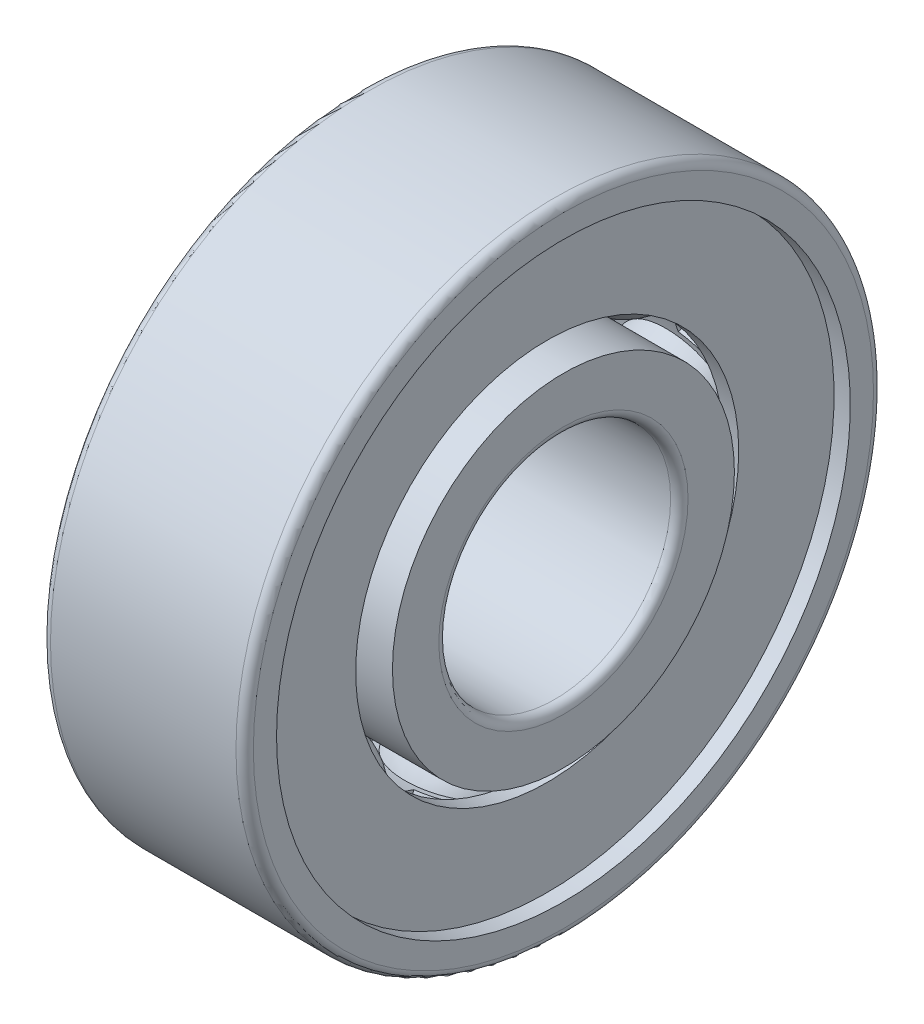
SolidWorks part; units mm, degrees
revolve "凸台-旋转2" add sketch "草图6" angle 360 about L4
sketch "草图6" plane through (0, 0, 0) normal (0, 0, 1) x (1, 0, 0)
  line L0 (0, 0) -> (5.5439, 0) construction
  line L1 (-12.4206, 0) -> (9.8128, 0) construction
  line L2 (0, 0) -> (0, 11.4011) construction
  line L3 (-5.5681, 7.9) -> (6.1049, 7.9) construction
  line L4 (-5.5681, 7.9) -> (6.1049, 7.9) construction
  line L5 (-2.15, 7.9) -> (2.15, 7.9)
  arc A0 (-2.15, 7.9) -> (2.15, 7.9) centre (0, 7.9) ccw
  dimension "Dw" = 4.3
revolve "基体-旋转" add sketch "草图2" angle 360 about L0
sketch "草图2" plane through (0, 0, 0) normal (0, 0, 1) x (1, 0, 0)
  line L0 (-12.4206, 0) -> (9.8128, 0) construction
  line L1 (0, 0) -> (0, 37.3563) construction
  line L2 (-5.5681, 7.9) -> (6.1049, 7.9) construction
  line L3 (-0.473, 8.4913) -> (0.473, 8.4913)
  line L4 (-0.473, 8.4913) -> (-0.473, 7.3088)
  line L5 (-0.473, 7.3088) -> (0.473, 7.3088)
  line L6 (0.473, 8.4913) -> (0.473, 7.3088)
  dimension "D1" = 0.946
  dimension "D2" = 0.473
  dimension "D3" = 1.1825
  dimension "D4" = 0.5913
  dimension "D5" = 7.9
revolve "凸台-旋转1" add sketch "草图3" angle 360 about L1
sketch "草图3" plane through (0, 0, 0) normal (0, 0, 1) x (1, 0, 0)
  line L0 (-5.5681, 7.9) -> (6.1049, 7.9) construction
  line L1 (-5.5681, 7.9) -> (6.1049, 7.9) construction
  line L2 (-12.4206, 0) -> (9.8128, 0) construction
  line L3 (-12.4206, 0) -> (9.8128, 0) construction
  line L4 (0, 0) -> (0, 37.3563) construction
  line L5 (0, 0) -> (0, 37.3563) construction
  line L6 (-2.365, 7.9) -> (2.365, 7.9)
  arc A0 (-2.365, 7.9) -> (2.365, 7.9) centre (0, 7.9) ccw
  dimension "Dwww" = 4.73
  dimension "D2" = 2.365
pattern_circular "阵列(圆周)1" count 8 over 360 about axis through (-12.4206, 0, 0) along (1, 0, 0) of "凸台-旋转1"
revolve "凸台-旋转3" add sketch "草图7" angle 360 about L0
sketch "草图7" plane through (0, 0, 0) normal (0, 0, 1) x (1, 0, 0)
  line L0 (0, 0) -> (6.6488, 0) construction
  line L1 (0, 0) -> (0, 16.8954) construction
  line L2 (-3.2, 11) -> (3.2, 11)
  line L3 (-3.5, 10.7) -> (-3.5, 9.9)
  line L4 (-3.5, 9.9) -> (-0.7613, 9.9)
  line L5 (3.5, 10.7) -> (3.5, 9.9)
  line L6 (0.7613, 9.9) -> (2.4048, 9.9)
  line L7 (2.94, 9.9) -> (3.5, 9.9)
  line L8 (2.4048, 9.65) -> (2.94, 9.65)
  line L9 (2.4048, 9.65) -> (2.4048, 9.9)
  line L11 (2.94, 9.65) -> (2.94, 9.9)
  arc A0 (-3.2, 11) -> (-3.5, 10.7) centre (-3.2, 10.7) ccw
  arc A1 (3.2, 11) -> (3.5, 10.7) centre (3.2, 10.7) cw
  arc A2 (2.0671, 8.4912) -> (-2.0671, 8.4913) centre (0, 7.9) ccw construction
  arc A3 (0.789, 9.9) -> (-0.0001, 10.05) centre (0, 7.9) ccw construction
  arc A4 (0.7613, 9.9) -> (-0.7613, 9.9) centre (0, 7.9) ccw
  point P10 (-3.5, 11)
  point P13 (3.5, 11)
  dimension "D3" = 3.5
  dimension "D4" = 0.5352
  dimension "D5" = 19.3
  dimension "D6" = 0.56
  dimension "B" = 7
ref_plane "基准面1" through (0, 0, 0) normal (0, 0, 1) x (1, 0, 0)
ref_plane "基准面2" through (0, 0, 0) normal (0, 1, 0) x (1, 0, 0)
ref_plane "基准面3" through (0, 0, 0) normal (1, 0, 0) x (0, 0, -1)
sketch "尺寸草图" plane through (0, 0, 0) normal (0, 0, 1) x (1, 0, 0)
  point P0 (0, -75.4307)
  point P1 (4.3, -75.4307)
  point P2 (0, 50.7088)
  point P3 (8, 50.7088)
  point P4 (22, 50.7088)
  point P5 (7, 50.7088)
  point P6 (0, -10.9899)
  point P7 (11.8, -10.9899)
  point P8 (19.3, -10.9899)
  point P9 (0.3, -10.9899)
  point P10 (8, -75.4307)
  dimension "B" = 7
sketch "草图4" plane through (0, 0, 0) normal (0, 0, 1) x (1, 0, 0)
  line L0 (0, 0) -> (8.1272, 0) construction
  line L1 (-12.4206, 0) -> (9.8128, 0) construction
  line L3 (-0.473, 8.4913) -> (0.473, 8.4913) construction
  line L4 (-2.365, 10.8563) -> (2.365, 10.8563)
  line L5 (-2.365, 10.8563) -> (-2.365, 8.4913)
  line L6 (-2.365, 8.4913) -> (2.365, 8.4913)
  line L7 (2.365, 10.8563) -> (2.365, 8.4913)
revolve "切除-旋转1" cut sketch "草图4" angle 360 about L0
sketch "草图5" plane through (0, 0, 0) normal (0, 0, 1) x (1, 0, 0)
  line L0 (0, 0) -> (8.2665, 0) construction
  line L1 (-12.4206, 0) -> (9.8128, 0) construction
  line L2 (-0.473, 7.3088) -> (0.473, 7.3088) construction
  line L3 (-2.365, 7.3088) -> (2.365, 7.3088)
  line L4 (-2.365, 7.3088) -> (-2.365, 4.9438)
  line L5 (-2.365, 4.9438) -> (2.365, 4.9438)
  line L6 (2.365, 7.3088) -> (2.365, 4.9438)
revolve "切除-旋转2" cut sketch "草图5" angle 360 about L0
pattern_circular "阵列(圆周)2" count 8 over 360 about axis through (-12.4206, 0, 0) along (1, 0, 0) of "凸台-旋转2"
sketch "草图8" plane through (0, 0, 0) normal (0, 0, 1) x (1, 0, 0)
  line L0 (-12.4206, 0) -> (9.8128, 0) construction
  line L1 (-12.4206, 0) -> (9.8128, 0) construction
  line L2 (3.5, 10.7) -> (3.5, 9.9) construction
  line L3 (-3.5, 5.9) -> (-0.7613, 5.9)
  line L4 (-3.5, 5.9) -> (-3.5, 4.3)
  line L5 (-3.2, 4) -> (3.2, 4)
  line L6 (3.5, 5.9) -> (3.5, 4.3)
  line L7 (-3.5, 10.7) -> (-3.5, 9.9) construction
  line L8 (0.7613, 5.9) -> (3.5, 5.9)
  arc A0 (-3.5, 4.3) -> (-3.2, 4) centre (-3.2, 4.3) ccw
  arc A1 (3.2, 4) -> (3.5, 4.3) centre (3.2, 4.3) ccw
  arc A2 (-2.0671, 7.3087) -> (2.0671, 7.3087) centre (0, 7.9) ccw construction
  arc A3 (-2.0671, 7.3087) -> (2.0671, 7.3087) centre (0, 7.9) ccw construction
  arc A4 (-0.7613, 5.9) -> (0.7613, 5.9) centre (0, 7.9) ccw
  dimension "D1" = 0.3
  dimension "DD" = 8
  dimension "D2" = 0.01
revolve "凸台-旋转4" add sketch "草图8" angle 360 about L1
sketch "草图10" plane through (0, 0, 0) normal (0, 0, 1) x (1, 0, 0)
  line L0 (2.4048, 9.9) -> (2.4048, -9.9) construction
  line L1 (2.94, 9.65) -> (2.4048, 9.65)
  line L2 (2.94, 9.65) -> (2.94, 6.6095)
  line L3 (2.94, 6.6095) -> (2.4048, 6.6095)
  line L4 (2.4048, 9.65) -> (2.4048, 6.6095)
  line L5 (0.7613, 5.9) -> (3.5, 5.9) construction
  line L6 (0, 0) -> (-5.3515, 0) construction
  line L7 (-12.4206, 0) -> (9.8128, 0) construction
  dimension "D1" = 0.7095
revolve "凸台-旋转5" add sketch "草图10" angle 360 about L6
sketch "草图11" plane through (0, 0, 0) normal (1, 0, 0) x (0, 0, -1)
  circle A0 centre (0, 0) radius 11
  circle A1 centre (0, 0) radius 11 construction
extrude "切除-拉伸1" cut sketch "草图11" against normal blind 10
mirror "镜向所有1" about plane through (0, 0, 0) normal (1, 0, 0) of bodies 109
equation "\"D5@草图7\" = \"防尘圈径D3@尺寸草图\""
equation "\"Z@阵列(圆周)1\"=\"球数Z@尺寸草图\" "
equation "\"Dw@草图6\"=\"球径DW@尺寸草图\""
equation "\"DD@草图8\"=\"d@尺寸草图\""
equation "\"D@草图7\"=\"DD@尺寸草图\""
equation "\"B@草图7\"=\"B@尺寸草图\" "
equation "\"DD2@草图8\"=\"内圈外径DD2@尺寸草图\""
equation "\"R@草图7\"=\"r@尺寸草图\""
equation "\"D3@草图2\" = 0.25*\"Dwww@草图3\""
equation "\"D4@草图2\" = \"D3@草图2\"/2"
equation "\"Dwww@草图3\" = 1.1*\"Dw@草图6\""
equation "\"D2@草图3\" = 0.5*\"Dwww@草图3\""
equation "\"D1@草图2\" = 0.2*\"Dwww@草图3\""
equation "\"D2@草图2\" = 0.5*\"D1@草图2\""
equation "\"切除位置@草图4\" = \"Dwww@草图3\"/2"
equation "\"D1@阵列(圆周)2\" = \"Z@阵列(圆周)1\""
equation "\"D3@草图7\" = \"B@草图7\" / 2"
equation "\"D1@草图8\" = \"R@草图7\""
equation "\"D2@草图7\" = 0.9*\"D@草图7\""
equation "\"D5@草图2\" = 0.25* ( \"D2@草图7\" + \"DD2@草图8\" )  "
equation "\"D6@草图7\" = 0.08 * \"B@草图7\""
equation "\"D1@草图10\" = 0.15*\"Dwww@草图3\""
